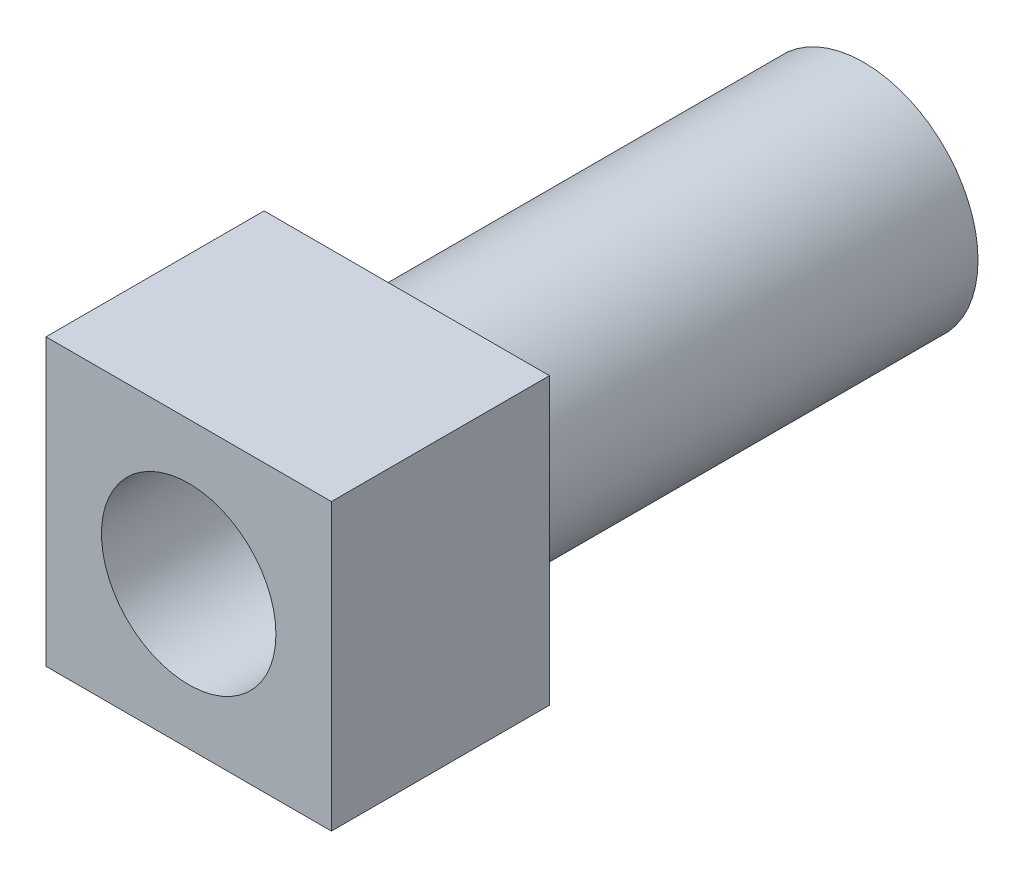
SolidWorks part; units mm, degrees
ref_plane "Plan de face" through (0, 0, 0) normal (0, 0, 1) x (1, 0, 0)
ref_plane "Plan de dessus" through (0, 0, 0) normal (0, 1, 0) x (1, 0, 0)
ref_plane "Plan de droite" through (0, 0, 0) normal (1, 0, 0) x (0, 0, -1)
sketch "Esquisse1" plane through (0, 0, 0) normal (0, 0, 1) x (1, 0, 0)
  line L1 (-37.0561, 15.4804) -> (-23.3161, 15.4804)
  line L2 (-37.0561, 15.4804) -> (-37.0561, 1.7404)
  line L3 (-37.0561, 1.7404) -> (-23.3161, 1.7404)
  line L4 (-23.3161, 15.4804) -> (-23.3161, 1.7404)
  dimension "D1" = 13.74
  dimension "D2" = 13.74
extrude "Boss.-Extru.1" add sketch "Esquisse1" along normal blind 10.5
sketch "Esquisse2" plane through (0, 0, 0) normal (0, 0, -1) x (-1, 0, 0)
  circle A1 centre (30.1861, 8.6104) radius 2.49
sketch "Esquisse3" plane through (0, 0, 10.5) normal (0, 0, 1) x (1, 0, 0)
  circle A0 centre (-30.1861, 8.6104) radius 4.2
extrude "Enlèv. mat.-Extru.2" cut sketch "Esquisse3" against normal blind 10
extrude "Boss.-Extru.4" add sketch "Esquisse2" along normal blind 22
sketch "Esquisse5" plane through (0, 0, -22) normal (0, 0, -1) x (-1, 0, 0)
  line L0 (27.6961, 8.6104) -> (29.6258, 11.0365)
  circle A0 centre (30.1861, 8.6104) radius 2.49 construction
  arc A1 (27.6961, 8.6104) -> (29.6258, 11.0365) centre (30.1861, 8.6104) ccw
  spline S0 degree 1 poles (29.6258, 11.0365) (27.6961, 8.6104) knots 0 0 1 1
  circle M2 centre (30.1861, 8.6104) radius 2.49
  dimension "D1" = 3.1
extrude "Enlèv. mat.-Extru.4" cut sketch "Esquisse5" against normal blind 22 contours L0 M2 region at (-30.2921, 8.5261, -22)
sketch "Esquisse6" plane through (0, 0, 0) normal (0, 0, -1) x (-1, 0, 0)
  circle A0 centre (30.1861, 8.6104) radius 5.5
  circle A2 centre (30.1861, 8.6104) radius 2.49
extrude "Boss.-Extru.5" add sketch "Esquisse6" along normal blind 22
